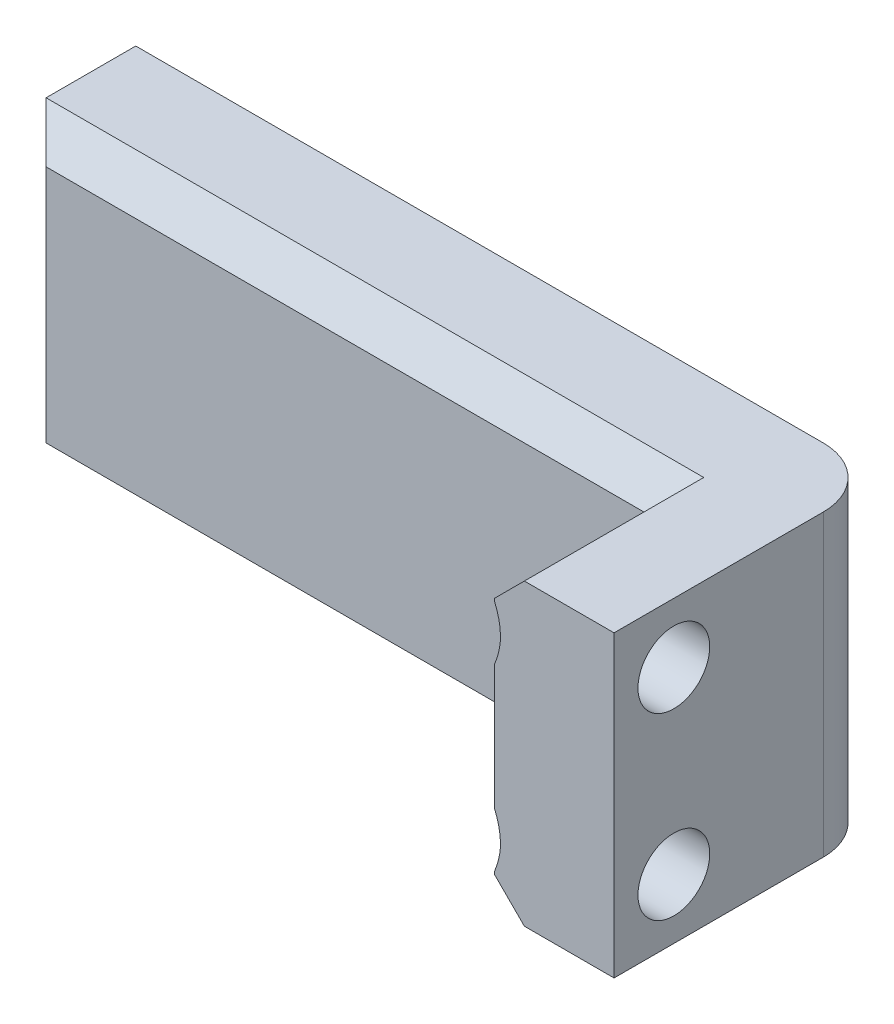
SolidWorks part; units mm, degrees
material "Liga 1060"
ref_plane "Plano frontal" through (0, 0, 0) normal (0, 0, 1) x (1, 0, 0)
ref_plane "Plano superior" through (0, 0, 0) normal (0, 1, 0) x (1, 0, 0)
ref_plane "Plano direito" through (0, 0, 0) normal (1, 0, 0) x (0, 0, -1)
sketch "Esboço1" plane through (0, 0, 0) normal (0, 0, 1) x (1, 0, 0)
  line L1 (0, 0) -> (25, 0)
  line L2 (0, 0) -> (0, 14)
  line L3 (0, 14) -> (25, 14)
  line L4 (25, 0) -> (25, 14)
  dimension "D1" = 14
  dimension "D2" = 25
extrude "Ressalto-extrusão1" add sketch "Esboço1" along normal blind 4 contours L2 L3 L4 L1
sketch "Esboço2" plane through (0, 0, 4) normal (0, 0, 1) x (1, 0, 0)
  line L0 (0, 0) -> (25, 0) construction
  line L1 (25, 14) -> (21, 14)
  line L2 (25, 14) -> (25, 0)
  line L3 (25, 0) -> (21, 0)
  line L4 (21, 14) -> (21, 0)
  dimension "D1" = 4
extrude "Ressalto-extrusão2" add sketch "Esboço2" along normal blind 5
sketch "Esboço4" plane through (0, 0, 9) normal (0, 0, 1) x (1, 0, 0)
  line L0 (25, 14) -> (25, 12)
  line L1 (25, 0) -> (25, 14) construction
  line L2 (25, 12) -> (0, 12)
  line L3 (0, 12) -> (0, 14)
  line L4 (0, 14) -> (21, 14) construction
  line L5 (0, 14) -> (25, 14)
  line L6 (25, 0) -> (0, 0)
  line L7 (0, 0) -> (21, 0) construction
  line L8 (0, 0) -> (0, 2)
  line L9 (0, 2) -> (25, 2)
  line L10 (25, 2) -> (25, 0)
  line L11 (0, 0) -> (0, 14) construction
  dimension "D1" = 2
extrude "Corte-extrusão1" cut sketch "Esboço4" against normal through all
sketch "Esboço6" plane through (21, 0, 0) normal (-1, 0, 0) x (0, 0, 1)
  line L0 (9, 12) -> (9, 2) construction
  line L1 (9, 7) -> (9, 12) construction
  line L2 (9, 7) -> (7, 10) construction
  line L3 (9, 7) -> (8, 7) construction
  line L4 (9, 7) -> (7, 4) construction
  point P1 (0, 0)
  dimension "D1" = 3
  dimension "D2" = 3
  dimension "D3" = 2
hole_wizard "Escareado para parafuso com cabeça escareada chata de M21" positions "3DSketch2" profile "Esboço8" countersink size "M2" standard "ISO"
sketch3d "3DSketch2"
  point P0 (21, 10, 7)
  point P3 (21, 4, 7)
sketch "Esboço8" plane through (21, 10, 7) normal (0, 1, 0) x (0, 0, 1)
  line L0 (0, 0) -> (0, 15.721)
  line L1 (0, 15.721) -> (1.2, 15)
  line L2 (1.2, 15) -> (1.2, 1)
  line L3 (1.2, 1) -> (2.2, 0)
  line L5 (2.2, 0) -> (0, 0)
  line L6 (-1.2, 1) -> (-2.2, 0) construction
  line L10 (0, 15.721) -> (-1.2, 15) construction
  line L11 (0, -6.35) -> (0, 107.95) construction
  dimension "Hole Dia." = 2.4
  dimension "Hole Depth" = 15
  dimension "Near C'Sink Dia." = 4.4
  dimension "Near C'Sink Angle" = 90
  dimension "Drill Angle" = 118
fillet "Filete1" radius 2 1 edges at (25, 7, 0)
chamfer "Chanfro1" distance 1 angle 45 5 edges at (10.5, 2, 4) (0, 7, 4) (10.5, 12, 4) (21, 2, 5.0417) (21, 12, 5.0417)
